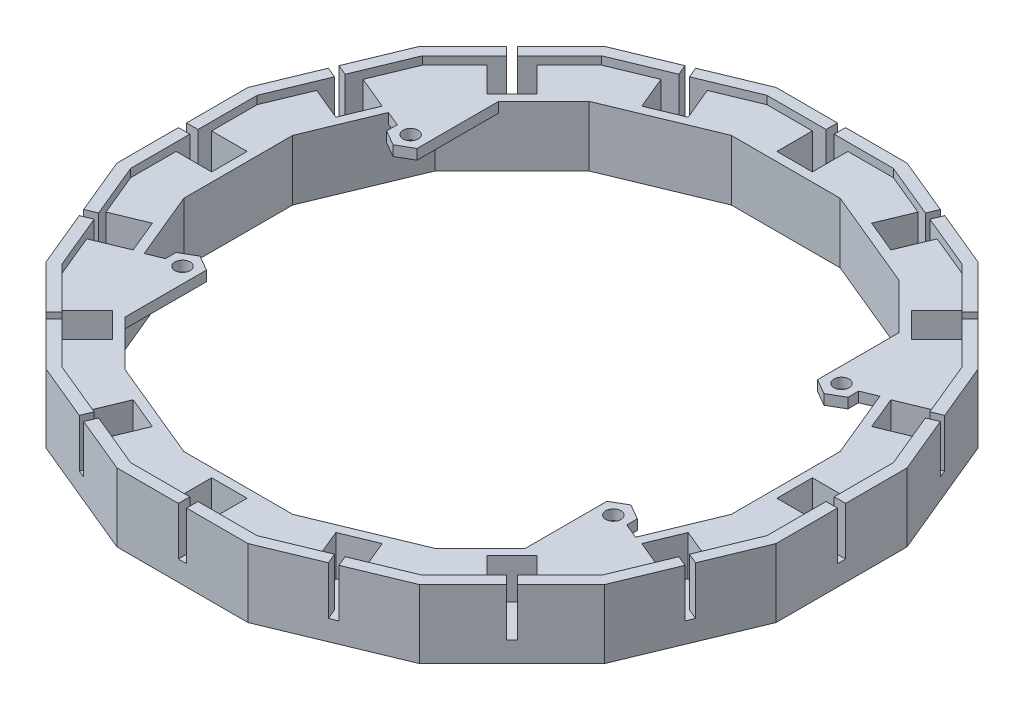
SolidWorks part; units mm, degrees
ref_plane "Front Plane" through (0, 0, 0) normal (0, 0, 1) x (1, 0, 0)
ref_plane "Top Plane" through (0, 0, 0) normal (0, 1, 0) x (1, 0, 0)
ref_plane "Right Plane" through (0, 0, 0) normal (1, 0, 0) x (0, 0, -1)
sketch "Sketch1" plane through (0, 0, 0) normal (0, 1, 0) x (1, 0, 0)
  line L19 (55.1043, 36.8195) -> (36.8195, 55.1043)
  line L20 (36.8195, 55.1043) -> (12.9293, 65)
  line L21 (12.9293, 65) -> (-12.9293, 65)
  line L22 (-12.9293, 65) -> (-36.8195, 55.1043)
  line L23 (-36.8195, 55.1043) -> (-55.1043, 36.8195)
  line L24 (-55.1043, 36.8195) -> (-65, 12.9293)
  line L25 (-65, 12.9293) -> (-65, -12.9293)
  line L26 (-65, -12.9293) -> (-55.1043, -36.8195)
  line L27 (-55.1043, -36.8195) -> (-36.8195, -55.1043)
  line L28 (-36.8195, -55.1043) -> (-12.9293, -65)
  line L29 (-12.9293, -65) -> (12.9293, -65)
  line L30 (12.9293, -65) -> (36.8195, -55.1043)
  line L31 (36.8195, -55.1043) -> (55.1043, -36.8195)
  line L32 (55.1043, -36.8195) -> (65, -12.9293)
  line L33 (65, -12.9293) -> (65, 12.9293)
  line L34 (65, 12.9293) -> (55.1043, 36.8195)
  line L35 (10.7413, 54) -> (-10.7413, 54)
  line L36 (-10.7413, 54) -> (-30.5885, 45.779)
  line L37 (-30.5885, 45.779) -> (-45.779, 30.5885)
  line L38 (-45.779, 30.5885) -> (-54, 10.7413)
  line L39 (-54, 10.7413) -> (-54, -10.7413)
  line L40 (-54, -10.7413) -> (-45.779, -30.5885)
  line L41 (-45.779, -30.5885) -> (-30.5885, -45.779)
  line L42 (-30.5885, -45.779) -> (-10.7413, -54)
  line L43 (-10.7413, -54) -> (10.7413, -54)
  line L44 (10.7413, -54) -> (30.5885, -45.779)
  line L45 (30.5885, -45.779) -> (45.779, -30.5885)
  line L46 (45.779, -30.5885) -> (54, -10.7413)
  line L47 (54, -10.7413) -> (54, 10.7413)
  line L48 (54, 10.7413) -> (45.779, 30.5885)
  line L49 (45.779, 30.5885) -> (30.5885, 45.779)
  line L50 (30.5885, 45.779) -> (10.7413, 54)
  circle A0 centre (0, 0) radius 65 construction
  circle A1 centre (0, 0) radius 54 construction
  dimension "D1" = 130
  dimension "D2" = 11
extrude "Boss-Extrude1" add sketch "Sketch1" along normal blind 13.5
sketch "Sketch2" plane through (0, 13.5, 0) normal (0, 1, 0) x (1, 0, 0)
  line L1 (35.545, 53.1969) -> (12.4818, 62.75)
  line L2 (12.4818, 62.75) -> (-12.4818, 62.75)
  line L3 (-12.4818, 62.75) -> (-35.545, 53.1969)
  line L4 (-35.545, 53.1969) -> (-53.1969, 35.545)
  line L5 (-53.1969, 35.545) -> (-62.75, 12.4818)
  line L6 (-62.75, 12.4818) -> (-62.75, -12.4818)
  line L7 (-62.75, -12.4818) -> (-53.1969, -35.545)
  line L8 (-53.1969, -35.545) -> (-35.545, -53.1969)
  line L9 (-35.545, -53.1969) -> (-12.4818, -62.75)
  line L10 (-12.4818, -62.75) -> (12.4818, -62.75)
  line L11 (12.4818, -62.75) -> (35.545, -53.1969)
  line L12 (35.545, -53.1969) -> (53.1969, -35.545)
  line L13 (53.1969, -35.545) -> (62.75, -12.4818)
  line L14 (62.75, -12.4818) -> (62.75, 12.4818)
  line L15 (62.75, 12.4818) -> (53.1969, 35.545)
  line L16 (53.1969, 35.545) -> (35.545, 53.1969)
  circle A0 centre (0, 0) radius 62.75 construction
  dimension "D1" = 125.5
extrude "Cut-Extrude1" cut sketch "Sketch2" against normal blind 1.6
sketch "Sketch3" plane through (0, 13.5, 0) normal (0, 1, 0) x (1, 0, 0)
  line L0 (12.4818, 62.75) -> (-12.4818, 62.75) construction
  line L1 (-3.5, 62.75) -> (-0.8, 62.75)
  line L2 (-3.5, 62.75) -> (-3.5, 55.75)
  line L3 (-3.5, 55.75) -> (3.5, 55.75)
  line L4 (3.5, 62.75) -> (3.5, 55.75)
  line L5 (12.9293, 65) -> (-12.9293, 65) construction
  line L7 (-0.8, 62.75) -> (-0.8, 65)
  line L8 (-0.8, 65) -> (0.8, 65)
  line L9 (0.8, 62.75) -> (0.8, 65)
  line L10 (0.8, 62.75) -> (3.5, 62.75)
  line L11 (20.7798, 59.3128) -> (23.2743, 58.2796)
  line L12 (23.2743, 58.2796) -> (24.1353, 60.3583)
  line L13 (24.1353, 60.3583) -> (25.6135, 59.746)
  line L14 (24.7525, 57.6673) -> (25.6135, 59.746)
  line L15 (24.7525, 57.6673) -> (27.247, 56.634)
  line L16 (27.247, 56.634) -> (24.5682, 50.1669)
  line L17 (18.101, 52.8457) -> (24.5682, 50.1669)
  line L18 (20.7798, 59.3128) -> (18.101, 52.8457)
  line L19 (41.8961, 46.8458) -> (43.8053, 44.9366)
  line L20 (43.8053, 44.9366) -> (45.3963, 46.5276)
  line L21 (45.3963, 46.5276) -> (46.5276, 45.3963)
  line L22 (44.9366, 43.8053) -> (46.5276, 45.3963)
  line L23 (44.9366, 43.8053) -> (46.8458, 41.8961)
  line L24 (46.8458, 41.8961) -> (41.8961, 36.9463)
  line L25 (36.9463, 41.8961) -> (41.8961, 36.9463)
  line L26 (41.8961, 46.8458) -> (36.9463, 41.8961)
  line L27 (56.634, 27.247) -> (57.6673, 24.7525)
  line L28 (57.6673, 24.7525) -> (59.746, 25.6135)
  line L29 (59.746, 25.6135) -> (60.3583, 24.1353)
  line L30 (58.2796, 23.2743) -> (60.3583, 24.1353)
  line L31 (58.2796, 23.2743) -> (59.3128, 20.7798)
  line L32 (59.3128, 20.7798) -> (52.8457, 18.101)
  line L33 (50.1669, 24.5682) -> (52.8457, 18.101)
  line L34 (56.634, 27.247) -> (50.1669, 24.5682)
  line L35 (62.75, 3.5) -> (62.75, 0.8)
  line L36 (62.75, 0.8) -> (65, 0.8)
  line L37 (65, 0.8) -> (65, -0.8)
  line L38 (62.75, -0.8) -> (65, -0.8)
  line L39 (62.75, -0.8) -> (62.75, -3.5)
  line L40 (62.75, -3.5) -> (55.75, -3.5)
  line L41 (55.75, 3.5) -> (55.75, -3.5)
  line L42 (62.75, 3.5) -> (55.75, 3.5)
  line L43 (59.3128, -20.7798) -> (58.2796, -23.2743)
  line L44 (58.2796, -23.2743) -> (60.3583, -24.1353)
  line L45 (60.3583, -24.1353) -> (59.746, -25.6135)
  line L46 (57.6673, -24.7525) -> (59.746, -25.6135)
  line L47 (57.6673, -24.7525) -> (56.634, -27.247)
  line L48 (56.634, -27.247) -> (50.1669, -24.5682)
  line L49 (52.8457, -18.101) -> (50.1669, -24.5682)
  line L50 (59.3128, -20.7798) -> (52.8457, -18.101)
  line L51 (46.8458, -41.8961) -> (44.9366, -43.8053)
  line L52 (44.9366, -43.8053) -> (46.5276, -45.3963)
  line L53 (46.5276, -45.3963) -> (45.3963, -46.5276)
  line L54 (43.8053, -44.9366) -> (45.3963, -46.5276)
  line L55 (43.8053, -44.9366) -> (41.8961, -46.8458)
  line L56 (41.8961, -46.8458) -> (36.9463, -41.8961)
  line L57 (41.8961, -36.9463) -> (36.9463, -41.8961)
  line L58 (46.8458, -41.8961) -> (41.8961, -36.9463)
  line L59 (27.247, -56.634) -> (24.7525, -57.6673)
  line L60 (24.7525, -57.6673) -> (25.6135, -59.746)
  line L61 (25.6135, -59.746) -> (24.1353, -60.3583)
  line L62 (23.2743, -58.2796) -> (24.1353, -60.3583)
  line L63 (23.2743, -58.2796) -> (20.7798, -59.3128)
  line L64 (20.7798, -59.3128) -> (18.101, -52.8457)
  line L65 (24.5682, -50.1669) -> (18.101, -52.8457)
  line L66 (27.247, -56.634) -> (24.5682, -50.1669)
  line L67 (3.5, -62.75) -> (0.8, -62.75)
  line L68 (0.8, -62.75) -> (0.8, -65)
  line L69 (0.8, -65) -> (-0.8, -65)
  line L70 (-0.8, -62.75) -> (-0.8, -65)
  line L71 (-0.8, -62.75) -> (-3.5, -62.75)
  line L72 (-3.5, -62.75) -> (-3.5, -55.75)
  line L73 (3.5, -55.75) -> (-3.5, -55.75)
  line L74 (3.5, -62.75) -> (3.5, -55.75)
  line L75 (-20.7798, -59.3128) -> (-23.2743, -58.2796)
  line L76 (-23.2743, -58.2796) -> (-24.1353, -60.3583)
  line L77 (-24.1353, -60.3583) -> (-25.6135, -59.746)
  line L78 (-24.7525, -57.6673) -> (-25.6135, -59.746)
  line L79 (-24.7525, -57.6673) -> (-27.247, -56.634)
  line L80 (-27.247, -56.634) -> (-24.5682, -50.1669)
  line L81 (-18.101, -52.8457) -> (-24.5682, -50.1669)
  line L82 (-20.7798, -59.3128) -> (-18.101, -52.8457)
  line L83 (-41.8961, -46.8458) -> (-43.8053, -44.9366)
  line L84 (-43.8053, -44.9366) -> (-45.3963, -46.5276)
  line L85 (-45.3963, -46.5276) -> (-46.5276, -45.3963)
  line L86 (-44.9366, -43.8053) -> (-46.5276, -45.3963)
  line L87 (-44.9366, -43.8053) -> (-46.8458, -41.8961)
  line L88 (-46.8458, -41.8961) -> (-41.8961, -36.9463)
  line L89 (-36.9463, -41.8961) -> (-41.8961, -36.9463)
  line L90 (-41.8961, -46.8458) -> (-36.9463, -41.8961)
  line L91 (-56.634, -27.247) -> (-57.6673, -24.7525)
  line L92 (-57.6673, -24.7525) -> (-59.746, -25.6135)
  line L93 (-59.746, -25.6135) -> (-60.3583, -24.1353)
  line L94 (-58.2796, -23.2743) -> (-60.3583, -24.1353)
  line L95 (-58.2796, -23.2743) -> (-59.3128, -20.7798)
  line L96 (-59.3128, -20.7798) -> (-52.8457, -18.101)
  line L97 (-50.1669, -24.5682) -> (-52.8457, -18.101)
  line L98 (-56.634, -27.247) -> (-50.1669, -24.5682)
  line L99 (-62.75, -3.5) -> (-62.75, -0.8)
  line L100 (-62.75, -0.8) -> (-65, -0.8)
  line L101 (-65, -0.8) -> (-65, 0.8)
  line L102 (-62.75, 0.8) -> (-65, 0.8)
  line L103 (-62.75, 0.8) -> (-62.75, 3.5)
  line L104 (-62.75, 3.5) -> (-55.75, 3.5)
  line L105 (-55.75, -3.5) -> (-55.75, 3.5)
  line L106 (-62.75, -3.5) -> (-55.75, -3.5)
  line L107 (-59.3128, 20.7798) -> (-58.2796, 23.2743)
  line L108 (-58.2796, 23.2743) -> (-60.3583, 24.1353)
  line L109 (-60.3583, 24.1353) -> (-59.746, 25.6135)
  line L110 (-57.6673, 24.7525) -> (-59.746, 25.6135)
  line L111 (-57.6673, 24.7525) -> (-56.634, 27.247)
  line L112 (-56.634, 27.247) -> (-50.1669, 24.5682)
  line L113 (-52.8457, 18.101) -> (-50.1669, 24.5682)
  line L114 (-59.3128, 20.7798) -> (-52.8457, 18.101)
  line L115 (-46.8458, 41.8961) -> (-44.9366, 43.8053)
  line L116 (-44.9366, 43.8053) -> (-46.5276, 45.3963)
  line L117 (-46.5276, 45.3963) -> (-45.3963, 46.5276)
  line L118 (-43.8053, 44.9366) -> (-45.3963, 46.5276)
  line L119 (-43.8053, 44.9366) -> (-41.8961, 46.8458)
  line L120 (-41.8961, 46.8458) -> (-36.9463, 41.8961)
  line L121 (-41.8961, 36.9463) -> (-36.9463, 41.8961)
  line L122 (-46.8458, 41.8961) -> (-41.8961, 36.9463)
  line L123 (-27.247, 56.634) -> (-24.7525, 57.6673)
  line L124 (-24.7525, 57.6673) -> (-25.6135, 59.746)
  line L125 (-25.6135, 59.746) -> (-24.1353, 60.3583)
  line L126 (-23.2743, 58.2796) -> (-24.1353, 60.3583)
  line L127 (-23.2743, 58.2796) -> (-20.7798, 59.3128)
  line L128 (-20.7798, 59.3128) -> (-18.101, 52.8457)
  line L129 (-24.5682, 50.1669) -> (-18.101, 52.8457)
  line L130 (-27.247, 56.634) -> (-24.5682, 50.1669)
  point P6 (0, 55.75)
  point P14 (0, 65)
  point P138 (0, 0)
  dimension "D1" = 7
  dimension "D2" = 1.6
  dimension "D4" = 55.75
  dimension "D5" = 3.5
  dimension "D3" = 16
extrude "Cut-Extrude2" cut sketch "Sketch3" against normal blind 9.5
sketch "Sketch5" plane through (0, 11.9, 0) normal (0, 1, 0) x (1, 0, 0)
  line L0 (-39.5, 24.2321) -> (-39.5, 36.8675)
  line L1 (-42.5, -22.5) -> (42.5, -22.5) construction
  line L2 (-42.5, -22.5) -> (-42.5, 22.5) construction
  line L3 (-42.5, 22.5) -> (42.5, 22.5) construction
  line L4 (42.5, -22.5) -> (42.5, 22.5) construction
  line L5 (-42.5, -22.5) -> (42.5, 22.5) construction
  line L6 (-42.5, 22.5) -> (42.5, -22.5) construction
  line L7 (-30.5885, 45.779) -> (-45.779, 30.5885) construction
  line L8 (-42.5, 19.0359) -> (-39.5, 20.7679)
  line L9 (-39.5, 20.7679) -> (-39.5, 24.2321)
  line L12 (-45.5, 24.2321) -> (-45.5, 20.7679)
  line L13 (-45.5, 20.7679) -> (-42.5, 19.0359)
  line L32 (-45.5, 24.2321) -> (-45.5, 30.8675)
  line L33 (-45.5, 30.8675) -> (-39.5, 36.8675)
  line L34 (-39.5, 24.2321) -> (-41, 25.0981)
  line L35 (-44, 25.0981) -> (-45.5, 24.2321)
  line L36 (-7.425, 0) -> (7.425, 0) construction
  line L37 (-45.5, -24.2321) -> (-45.5, -30.8675)
  line L38 (-45.5, -30.8675) -> (-39.5, -36.8675)
  line L39 (-39.5, -24.2321) -> (-39.5, -36.8675)
  line L40 (-39.5, -20.7679) -> (-39.5, -24.2321)
  line L41 (-42.5, -19.0359) -> (-39.5, -20.7679)
  line L42 (-45.5, -20.7679) -> (-42.5, -19.0359)
  line L43 (-45.5, -24.2321) -> (-45.5, -20.7679)
  line L44 (0, -7.425) -> (0, 7.425) construction
  line L45 (45.5, -24.2321) -> (45.5, -20.7679)
  line L46 (45.5, -20.7679) -> (42.5, -19.0359)
  line L47 (42.5, -19.0359) -> (39.5, -20.7679)
  line L48 (39.5, -20.7679) -> (39.5, -24.2321)
  line L49 (39.5, -24.2321) -> (39.5, -36.8675)
  line L50 (45.5, -30.8675) -> (39.5, -36.8675)
  line L51 (45.5, -24.2321) -> (45.5, -30.8675)
  line L52 (45.5, 24.2321) -> (45.5, 30.8675)
  line L53 (45.5, 30.8675) -> (39.5, 36.8675)
  line L54 (39.5, 24.2321) -> (39.5, 36.8675)
  line L55 (39.5, 20.7679) -> (39.5, 24.2321)
  line L56 (42.5, 19.0359) -> (39.5, 20.7679)
  line L57 (45.5, 20.7679) -> (42.5, 19.0359)
  line L58 (45.5, 24.2321) -> (45.5, 20.7679)
  circle A0 centre (-42.5, 22.5) radius 1.5
  arc A4 (-45.5, 22.5) -> (-39.5, 22.5) centre (-42.5, 22.5) ccw construction
  circle A5 centre (42.5, 22.5) radius 1.5
  circle A6 centre (42.5, -22.5) radius 1.5
  circle A7 centre (-42.5, -22.5) radius 1.5
  point P0 (0, 0)
  dimension "D3" = 3
  dimension "D4" = 6
  dimension "D1" = 85
  dimension "D2" = 45
  dimension "D5" = 12.6355
  dimension "D6" = 6.6355
extrude "Boss-Extrude2" add sketch "Sketch5" against normal blind 2
chamfer "Chamfer1" distance 8 4 edges at (45.5, 10.9, -30.8675) (45.5, 10.9, 30.8675) (-45.5, 10.9, 30.8675) (-45.5, 10.9, -30.8675)
